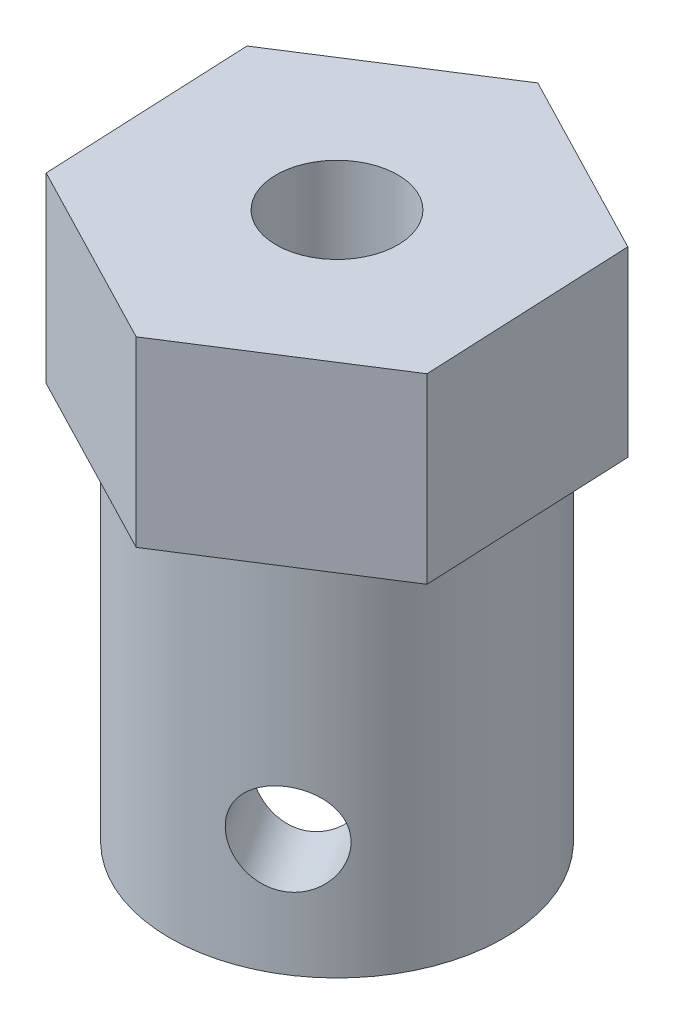
SolidWorks part; units mm, degrees
ref_plane "前视基准面" through (0, 0, 0) normal (0, 0, 1) x (1, 0, 0)
ref_plane "上视基准面" through (0, 0, 0) normal (0, 1, 0) x (1, 0, 0)
ref_plane "右视基准面" through (0, 0, 0) normal (1, 0, 0) x (0, 0, -1)
sketch "草图1" plane through (0, 0, 0) normal (0, 1, 0) x (1, 0, 0)
  line L1 (5.8371, 3.7321) -> (-0.3135, 6.9211)
  line L2 (-0.3135, 6.9211) -> (-6.1506, 3.189)
  line L3 (-6.1506, 3.189) -> (-5.8371, -3.7321)
  line L4 (-5.8371, -3.7321) -> (0.3135, -6.9211)
  line L5 (0.3135, -6.9211) -> (6.1506, -3.189)
  line L6 (6.1506, -3.189) -> (5.8371, 3.7321)
  circle A0 centre (0, 0) radius 6 construction
  circle A1 centre (0, 0) radius 2
  circle A2 centre (0, 0) radius 5.5
  circle A3 centre (0, 0) radius 3
  dimension "D1" = 12
extrude "凸台-拉伸1" add sketch "草图1" along normal blind 6 contours L4 L5 L6 L1 L2 L3 | A1
extrude "凸台-拉伸2" add sketch "草图1<3>" against normal blind 12 contours A2 | A3
sketch "草图1<3>" plane through (0, 0, 0) normal (0, 1, 0) x (1, 0, 0) same geometry as "草图1"
sketch "草图2" plane through (3.2321, 0, 5.0551) normal (0.5387, 0, 0.8425) x (0.8425, 0, -0.5387)
  circle A0 centre (0, -8.1353) radius 1.5
extrude "切除-拉伸1" cut sketch "草图2" against normal blind 30
